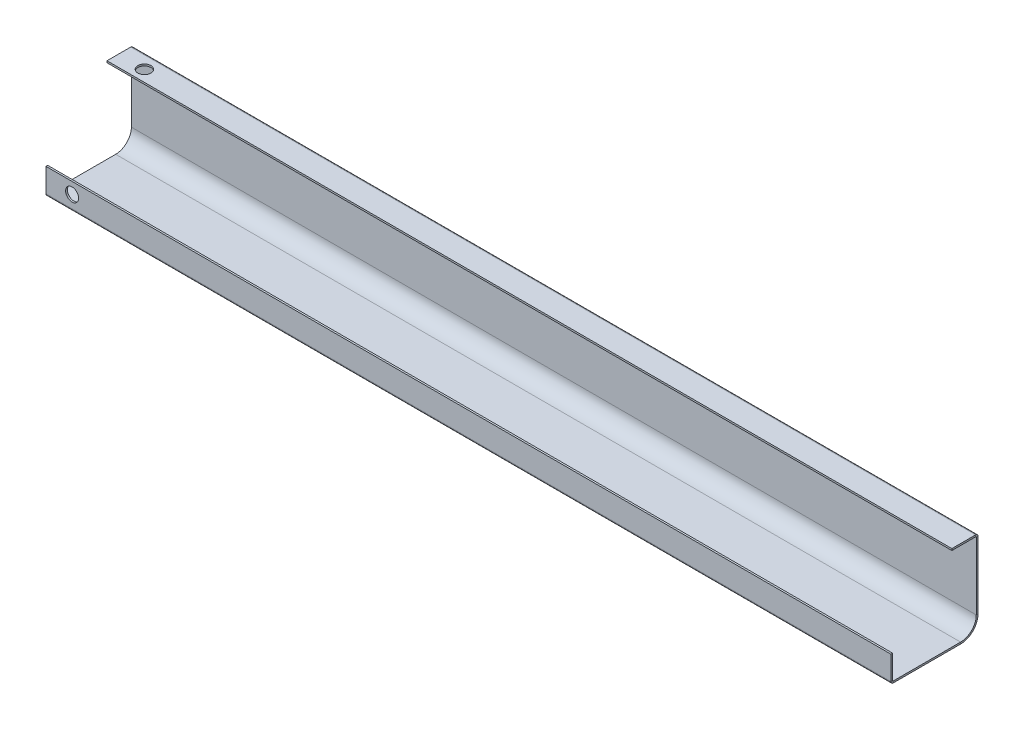
SolidWorks part; units mm, degrees
note: The reader was unsure of these and kept them because the rebuilt part matched: thickness of "基体-法兰1", "边线-法兰1", "边线-法兰2", "边线-法兰3", "钣金6", "钣金7", "钣金8", "钣金9", "钣金10", "钣金11"; flange length of "边线-法兰1", "边线-法兰2", "边线-法兰3".
ref_plane "前视基准面" through (0, 0, 0) normal (0, 0, 1) x (1, 0, 0)
ref_plane "上视基准面" through (0, 0, 0) normal (0, 1, 0) x (1, 0, 0)
ref_plane "右视基准面" through (0, 0, 0) normal (1, 0, 0) x (0, 0, -1)
sketch "草图2" plane through (0, 0, 0) normal (0, 0, 1) x (1, 0, 0)
  line L1 (-485, 50) -> (485, 50)
  line L2 (-485, 50) -> (-485, -50)
  line L3 (-485, -50) -> (485, -50)
  line L4 (485, 50) -> (485, -50)
  line L5 (-485, 50) -> (485, -50) construction
  line L6 (-485, -50) -> (485, 50) construction
  point P0 (0, 0)
  dimension "D1" = 970
  dimension "D2" = 100
base flange "基体-法兰1" sketch "草图2" thickness 2 reverse thickness direction no parameters "D1"=0.7366
edge flange "边线-法兰1" sketch "草图22" flange angle 90 flange length 100 flange position material inside bend radius 18 thickness 2 relief rectangular parameters "D6"=10
bend "边线折弯4" bend radius 18 bend angle 90 parameters "D5"=1
sketch "草图22" plane through (0, -50, 0) normal (0, 1, 0) x (-1, 0, 0)
  line L0 (-485, -2) -> (485, -2) construction
  line L1 (485, 0) -> (-485, 0) construction
  line L2 (-485, 0) -> (-485, 98)
  line L3 (-485, 98) -> (485, 98)
  line L4 (485, 98) -> (485, 0)
  line L5 (485, 0) -> (-485, 0)
  dimension "D1" = 100
edge flange "边线-法兰2" sketch "草图24" flange angle 90 flange length 30 flange position material inside bend radius 0.7366 thickness 2 relief rectangular parameters "D6"=10, "D8"=1
bend "边线折弯5" bend radius 0.7366 bend angle 90 parameters "D5"=2
sketch "草图24" plane through (0, 50, 0) normal (0, -1, 0) x (1, 0, 0)
  line L1 (485, 0) -> (-485, 0) construction
  line L2 (-485, 0) -> (-485, 28)
  line L3 (-485, 28) -> (485, 28)
  line L4 (485, 28) -> (485, 0)
  line L5 (485, 0) -> (-485, 0)
edge flange "边线-法兰3" sketch "草图27" flange angle 90 flange length 30 flange position material inside bend radius 0.7366 thickness 2 relief rectangular parameters "D6"=10
sketch "草图27" plane through (0, -48, 98) normal (0, 0, -1) x (-1, 0, 0)
  line L1 (485, 0) -> (-485, 0) construction
  line L2 (-485, 0) -> (-485, 28)
  line L3 (-485, 28) -> (485, 28)
  line L4 (485, 28) -> (485, 0)
  line L5 (485, 0) -> (-485, 0)
bend "边线折弯6" bend radius 0.7366 bend angle 90 parameters "D5"=3
sketch "草图16" plane through (0, 50, 0) normal (0, 1, 0) x (1, 0, 0)
  line L0 (485, -28) -> (-485, -28) construction
  line L2 (-485, -28) -> (-485, -0.7366) construction
  circle A0 centre (-455, -15) radius 7.5
  point P6 (-485, -14.3683)
  dimension "D3" = 15
  dimension "D1" = 13
  dimension "D2" = 30
extrude "切除-拉伸1" cut sketch "草图16" against normal blind 10 normal cut yes
sketch "草图17" plane through (0, 0, 98) normal (0, 0, 1) x (1, 0, 0)
  line L0 (-485, -47.2634) -> (-485, -20) construction
  line L2 (-485, -20) -> (485, -20) construction
  line L4 (-455, 7) -> (-455, -33) construction
  circle A0 centre (-455, -33) radius 7.5
  dimension "D3" = 15
  dimension "D1" = 13
  dimension "D2" = 30
extrude "切除-拉伸2" cut sketch "草图17" against normal blind 10 normal cut yes
sketch "折弯-线1" plane through (0, 0, 0) normal (0, 1, 0) x (1, 0, 0)
sketch "边界框1" plane through (0, 0, 0) normal (0, 1, 0) x (1, 0, 0)
sheet metal parameters "钣金6" thickness 2 parameters "D1"=0.7366, "D7"=1.5
flat pattern "平板型式6" [suppressed]
sketch "折弯-线2" plane through (0, 0, 0) normal (0, 1, 0) x (1, 0, 0)
sketch "边界框2" [suppressed] plane through (0, 0, 0) normal (0, 1, 0) x (1, 0, 0)
sheet metal parameters "钣金7" thickness 2 parameters "D1"=0.7366, "D7"=1.5
flat pattern "平板型式6" [suppressed]
sketch "折弯-线2" plane through (0, 0, 0) normal (0, 1, 0) x (1, 0, 0)
sketch "边界框2" [suppressed] plane through (0, 0, 0) normal (0, 1, 0) x (1, 0, 0)
bend of the flat pattern "展开-<边线折弯4>1"
sheet metal parameters "钣金8" thickness 2 parameters "D1"=0.7366, "D7"=1.5
flat pattern "平板型式6" [suppressed]
sketch "折弯-线2" plane through (0, 0, 0) normal (0, 1, 0) x (1, 0, 0)
sketch "边界框2" [suppressed] plane through (0, 0, 0) normal (0, 1, 0) x (1, 0, 0)
bend of the flat pattern "展开-<边线折弯4>2"
bend of the flat pattern "展开-<边线折弯5>1"
sheet metal parameters "钣金9" thickness 2 parameters "D1"=0.7366, "D7"=1.5
flat pattern "平板型式6" [suppressed]
sketch "折弯-线2" plane through (0, 0, 0) normal (0, 1, 0) x (1, 0, 0)
sketch "边界框2" [suppressed] plane through (0, 0, 0) normal (0, 1, 0) x (1, 0, 0)
bend of the flat pattern "展开-<边线折弯4>3"
bend of the flat pattern "展开-<边线折弯5>2"
bend of the flat pattern "展开-<边线折弯6>2"
sheet metal parameters "钣金10" thickness 2 parameters "D1"=0.7366, "D7"=1.5
flat pattern "平板型式6" [suppressed]
sketch "折弯-线2" plane through (0, 0, 0) normal (0, 0, 1) x (1, 0, 0)
  line L0 (-565, -107.0798) -> (565, -107.0798) construction
  line L1 (565, 38.02) -> (-565, 38.02) construction
  line L2 (-565, -34.5299) -> (565, -34.5299) construction
  line L3 (-565, -107.0798) -> (565, -107.0798) construction
  line L4 (565, 38.02) -> (-565, 38.02) construction
  line L5 (-565, -34.5299) -> (565, -34.5299) construction
sketch3d "边界框2" [suppressed]
  line L0 (-565, -155.0998, 0) -> (565, -155.0998, 0) construction
  line L1 (-565, 86.04, 0) -> (565, 86.04, 0) construction
  line L2 (-565, -155.0998, 0) -> (-565, 86.04, 0) construction
  line L3 (565, -155.0998, 0) -> (565, 86.04, 0) construction
bend of the flat pattern "展开-<边线折弯4>4"
bend of the flat pattern "展开-<边线折弯5>3"
bend of the flat pattern "展开-<边线折弯6>3"
sheet metal parameters "钣金11" thickness 2 parameters "D1"=0.7366, "D7"=1.5
flat pattern "平板型式6" [suppressed]
sketch "折弯-线2" plane through (0, 0, 0) normal (0, 1, 0) x (1, 0, 0)
sketch "边界框2" [suppressed] plane through (0, 0, 0) normal (0, 1, 0) x (1, 0, 0)
bend of the flat pattern "展开-<边线折弯4>2"
bend of the flat pattern "展开-<边线折弯5>1"
bend of the flat pattern "展开-<边线折弯6>1"
